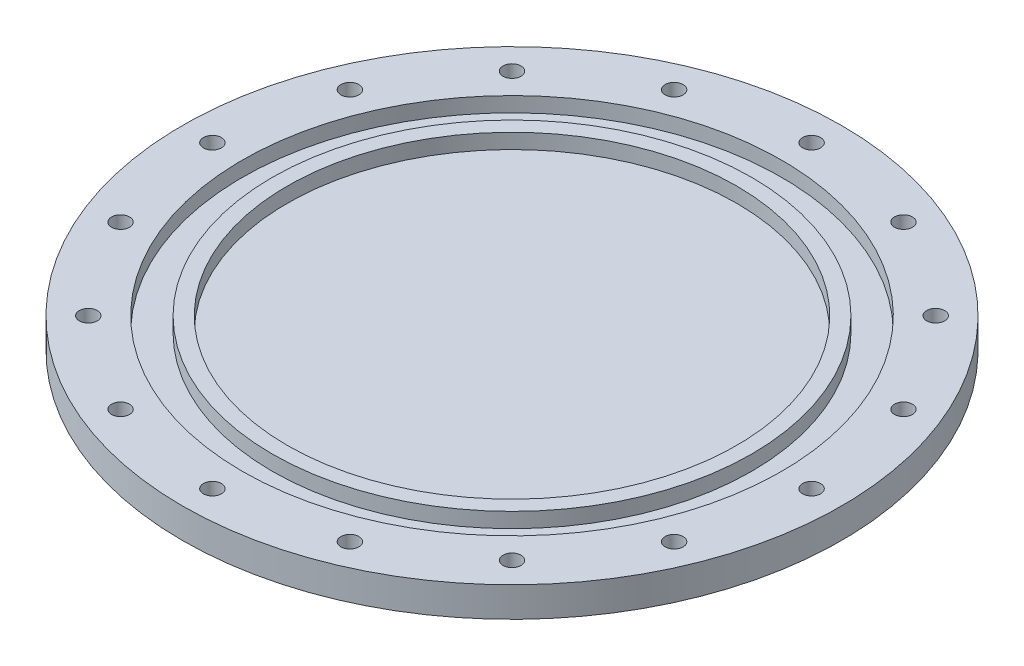
SolidWorks part; units mm, degrees
ref_plane "前视基准面" through (0, 0, 0) normal (0, 0, 1) x (1, 0, 0)
ref_plane "上视基准面" through (0, 0, 0) normal (0, 1, 0) x (1, 0, 0)
ref_plane "右视基准面" through (0, 0, 0) normal (1, 0, 0) x (0, 0, -1)
other "Configuration Table"
sketch "草图1" plane through (0, 0, 0) normal (0, 1, 0) x (1, 0, 0)
  circle A0 centre (0, 0) radius 75
  circle A1 centre (0, 0) radius 80
  circle A2 centre (0, 0) radius 90
  circle A3 centre (0, 0) radius 110
  circle A4 centre (0, 100) radius 3
  circle A5 centre (38.2683, 92.388) radius 3
  circle A6 centre (70.7107, 70.7107) radius 3
  circle A7 centre (92.388, 38.2683) radius 3
  circle A8 centre (100, 0) radius 3
  circle A9 centre (92.388, -38.2683) radius 3
  circle A10 centre (70.7107, -70.7107) radius 3
  circle A11 centre (38.2683, -92.388) radius 3
  circle A12 centre (0, -100) radius 3
  circle A13 centre (-38.2683, -92.388) radius 3
  circle A14 centre (-70.7107, -70.7107) radius 3
  circle A15 centre (-92.388, -38.2683) radius 3
  circle A16 centre (-100, 0) radius 3
  circle A17 centre (-92.388, 38.2683) radius 3
  circle A18 centre (-70.7107, 70.7107) radius 3
  circle A19 centre (-38.2683, 92.388) radius 3
  point P40 (0, 0)
  dimension "D1" = 150
  dimension "D2" = 160
  dimension "D3" = 180
  dimension "D4" = 220
  dimension "D5" = 6
  dimension "D6" = 100
  dimension "D7" = 16
extrude "凸台-拉伸1" add sketch "草图1" along normal blind 10 contours A3 A19 A18 A17 A16 A15 A14 A13 A12 A11 A10 A9 A8 A7 A6 A5 A4 A2 | A1 A0 region at (-77.7373, 0, 0) region at (-106.8887, 0, 0)
extrude "凸台-拉伸2" add sketch "草图1<3>" along normal blind 5 contours A2 A1 | A0 region at (0, 0, 0) region at (-87.4544, 0, 0)
sketch "草图1<3>" plane through (0, 0, 0) normal (0, 1, 0) x (1, 0, 0) same geometry as "草图1"
